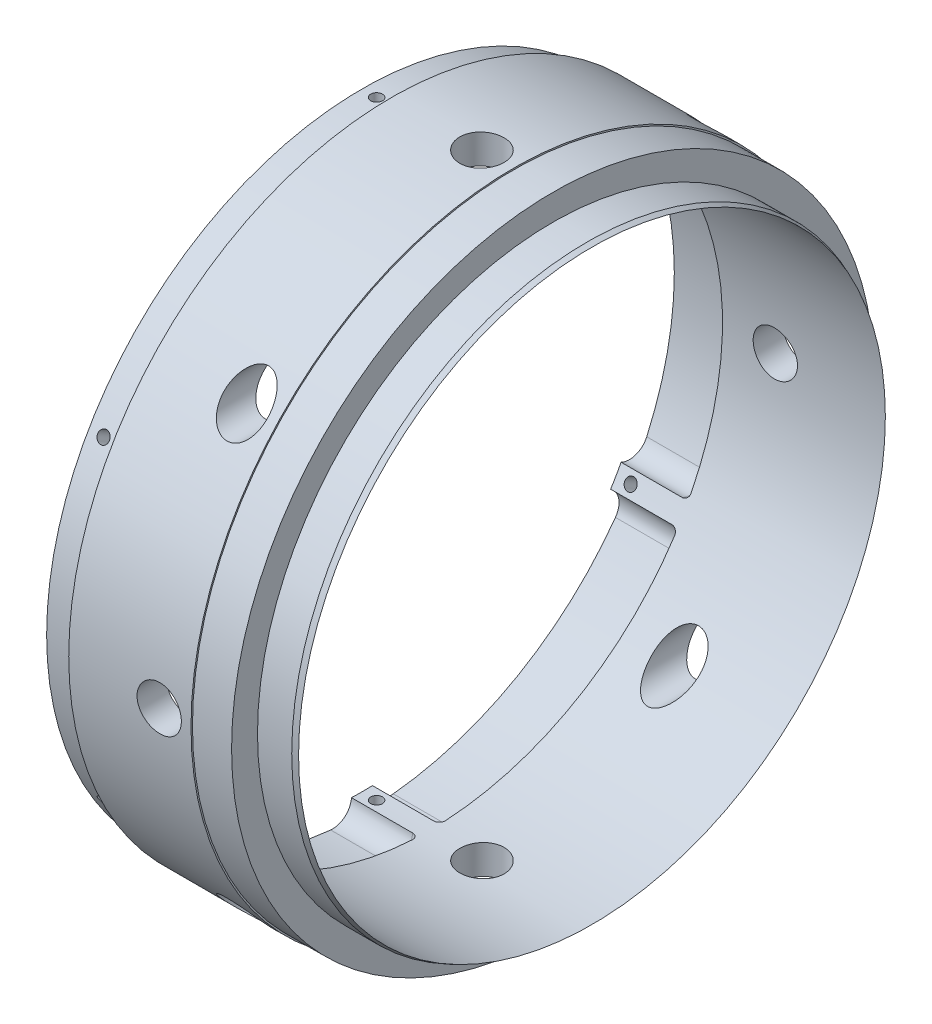
SolidWorks part; units mm, degrees
material "6061-T6 (SS)"
ref_plane "Front" through (0, 0, 0) normal (0, 0, 1) x (1, 0, 0)
ref_plane "Top" through (0, 0, 0) normal (0, 1, 0) x (1, 0, 0)
ref_plane "Right" through (0, 0, 0) normal (1, 0, 0) x (0, 0, -1)
sketch "Sketch1" plane through (0, 0, 0) normal (0, 0, 1) x (1, 0, 0)
  line L0 (-10.16, 0.508) -> (-1.27, 0.508)
  line L1 (-52.07, 7.62) -> (-20.32, 7.62)
  line L2 (-10.16, 7.239) -> (-10.16, 0.508)
  line L3 (0, 0) -> (-59.7408, 0)
  line L4 (-1.27, 0.508) -> (0, 0)
  line L5 (-59.7408, 5.6896) -> (-59.7408, 0)
  line L6 (-52.07, 7.62) -> (-52.07, 5.6896)
  line L7 (-52.07, 5.6896) -> (-59.7408, 5.6896)
  line L8 (-44.3099, -76.2) -> (29.4033, -76.2) construction
  line L9 (-20.32, 7.62) -> (-20.32, 7.239)
  line L10 (-20.32, 7.239) -> (-10.16, 7.239)
  dimension "D1" = 7.6708
  dimension "D2" = 0.508
  dimension "D3" = 31.75
  dimension "D4" = 10.16
  dimension "D5" = 76.2
  dimension "D6" = 5.6896
  dimension "D7" = 6.731
  dimension "D8" = 0.381
  dimension "D9" = 10.16
  dimension "D10" = 1.27
revolve "Revolve2" add sketch "Sketch1" angle 360 about L8
ref_point "Point1"
ref_plane "Plane1" through (0, -76.2, 0) normal (0, 1, 0) x (1, 0, 0)
ref_plane "Plane2" through (0, -158.0896, 0) normal (0, -1, 0) x (-1, 0, 0)
hole_wizard "#31 (0.12) Diameter Hole1" positions "3DSketch1" profile "Sketch11" hole size "#31" standard "ANSI Inch"
sketch3d "3DSketch1"
  point P0 (-55.9308, -158.0896, 0)
  dimension "D1" = 3.81
sketch "Sketch11" plane through (-55.9308, -158.0896, 0) normal (1, 0, 0) x (0, 0, -1)
  line L0 (0, 0) -> (0, 185.9821)
  line L1 (0, 185.9821) -> (1.524, 185.9821)
  line L2 (1.524, 185.9821) -> (1.524, 0)
  line L5 (1.524, 0) -> (0, 0)
  line L11 (0, -6.35) -> (0, 107.95) construction
  dimension "Thru Hole Dia." = 3.048
  dimension "Thru Hole Depth" = 185.9821
pattern_circular "CirPattern4" count 6 over 360 about axis through (-44.3099, -76.2, 0) along (-1, 0, 0) of "#31 (0.12) Diameter Hole1"
sketch "Sketch8" plane through (-59.7408, 0, 0) normal (-1, 0, 0) x (0, 0, 1)
  line L0 (-7.6343, -152.0166) -> (0, -76.2) construction
  line L1 (0, -76.2) -> (0, -152.4) construction
  line L2 (-61.8419, -120.7198) -> (0, -76.2) construction
  line L3 (0, -76.2) -> (-65.9911, -114.3) construction
  circle A0 centre (0, -76.2) radius 76.2 construction
  arc A1 (-65.841, -123.5988) -> (-8.128, -156.9194) centre (0, -76.2) ccw
  circle A2 centre (0, -76.2) radius 81.8896 construction
  circle A3 centre (0, -76.2) radius 76.2
  arc A4 (-64.5901, -116.6297) -> (-2.7181, -152.3515) centre (0, -76.2) ccw
  circle A5 centre (0, -76.2) radius 81.8896
  circle A6 centre (-61.8419, -120.7198) radius 4.9276
  circle A7 centre (-7.6343, -152.0166) radius 4.9276
  arc A8 (-1.524, -158.0754) -> (1.524, -158.0754) centre (0, -76.2) ccw construction
  arc A9 (-1.524, -152.3848) -> (1.524, -152.3848) centre (0, -76.2) ccw construction
  arc A10 (-1.524, -158.0754) -> (1.524, -158.0754) centre (0, -76.2) ccw
  arc A11 (-1.524, -152.3848) -> (1.524, -152.3848) centre (0, -76.2) ccw
  arc A12 (-64.5901, -116.6297) -> (-2.7181, -152.3515) centre (0, -76.2) ccw
  arc A13 (-66.7399, -112.9726) -> (-65.2159, -115.6122) centre (0, -76.2) ccw construction
  arc A14 (-66.7399, -112.9726) -> (-65.2159, -115.6122) centre (0, -76.2) ccw
  arc A15 (-71.6682, -115.8179) -> (-70.1442, -118.4575) centre (0, -76.2) ccw construction
  arc A16 (-71.6682, -115.8179) -> (-70.1442, -118.4575) centre (0, -76.2) ccw
  point P3 (0, -152.4)
  point P14 (-8.128, -156.9194)
  point P16 (-65.841, -123.5988)
  point P20 (-65.9911, -114.3)
  dimension "D2" = 5.75
  dimension "D3" = 0.762
  dimension "D4" = 5.75
  dimension "D1" = 0
extrude "Cut-Extrude1" cut sketch "Sketch8" against normal blind 17.4498
fillet "Fillet1" radius 1.5875 3 edges at (-42.291, -155.7816, -4.4553) (-42.291, -146.4586, -40.5638) (-42.291, -119.8492, -66.692)
pattern_circular "CirPattern3" count 6 over 360 about axis through (0, -76.2, 0) along (1, 0, 0) of "Cut-Extrude1", "Fillet1"
hole_wizard "1/2-20 Tapped Hole1" positions "3DSketch3" profile "Sketch12" tap size "1/2-20" standard "ANSI Inch" end condition up to next
sketch3d "3DSketch3"
  line L0 (0, 0, 0) -> (-28.575, 0, 0) construction
  line L1 (-28.575, 0, 0) -> (-28.575, 7.62, 0) construction
  line L3 (-28.575, 0, 0) -> (-28.575, -76.2, 0) construction
  line L4 (-28.575, -76.2, 0) -> (-28.575, -76.2, 83.82) construction
  arc A0 (-42.291, -41.8886, 68.038) -> (-42.291, -110.5114, 68.038) centre (-42.291, -76.2, 0) ccw construction
  point P0 (-28.575, -76.2, 83.82)
  point P2 (-28.575, -76.2, -83.82)
  point P4 (-28.575, 7.62, 0)
  point P6 (-28.575, -160.02, 0)
  point P29 (33.909, -76.2, 0)
  dimension "D1" = 28.575
sketch "Sketch12" plane through (-28.575, -76.2, 83.82) normal (1, 0, 0) x (0, -1, 0)
  line L0 (0, 0) -> (0, 7.62)
  line L1 (0, 7.62) -> (5.7544, 7.62)
  line L2 (5.7544, 7.62) -> (5.7544, 0)
  line L5 (5.7544, 0) -> (0, 0)
  line L11 (0, -6.35) -> (0, 107.95) construction
  dimension "Thru Tap Drill Dia." = 11.5087
  dimension "Thru Tap Drill Depth" = 7.62
cosmetic thread "Hole Thread1" parameters "D2"=12.7
cosmetic thread "Hole Thread2" parameters "D2"=12.7
cosmetic thread "Hole Thread3" parameters "D2"=12.7
cosmetic thread "Hole Thread4" parameters "D2"=12.7
hole_wizard "1/2-20 Tapped Hole2" positions "Sketch17" profile "Sketch16" tap size "1/2-20" standard "ANSI Inch"
sketch "Sketch17" plane through (0, 0, 0) normal (0, 0, 1) x (1, 0, 0)
  line L0 (-28.575, -76.2) -> (-28.575, -19.05) construction
  point P0 (-28.575, -19.05)
  dimension "D1" = 57.15
sketch "Sketch16" plane through (-28.575, -19.05, 0) normal (1, 0, 0) x (0, 1, 0)
  line L0 (0, 0) -> (0, 83.82)
  line L1 (0, 83.82) -> (5.7544, 83.82)
  line L2 (5.7544, 83.82) -> (5.7544, 0)
  line L5 (5.7544, 0) -> (0, 0)
  line L11 (0, -6.35) -> (0, 107.95) construction
  dimension "Thru Tap Drill Dia." = 11.5087
  dimension "Thru Tap Drill Depth" = 83.82
cosmetic thread "Hole Thread5" parameters "D2"=12.7
pattern_circular "CirPattern5" count 2 over 360 about axis through (-28.575, -76.2, 0) along (0, 0, 1) of "1/2-20 Tapped Hole2"
mirror "Mirror1" about plane through (0, 0, 0) normal (0, 0, 1) of "1/2-20 Tapped Hole2", "CirPattern5"
sketch3d "3DSketch2"
  circle A0 centre (-24.9799, -157.9493, -0.0042) radius 2.0193
  point P2 (-24.9799, -155.93, -0.0042)
  dimension "D1" = 4.0386
